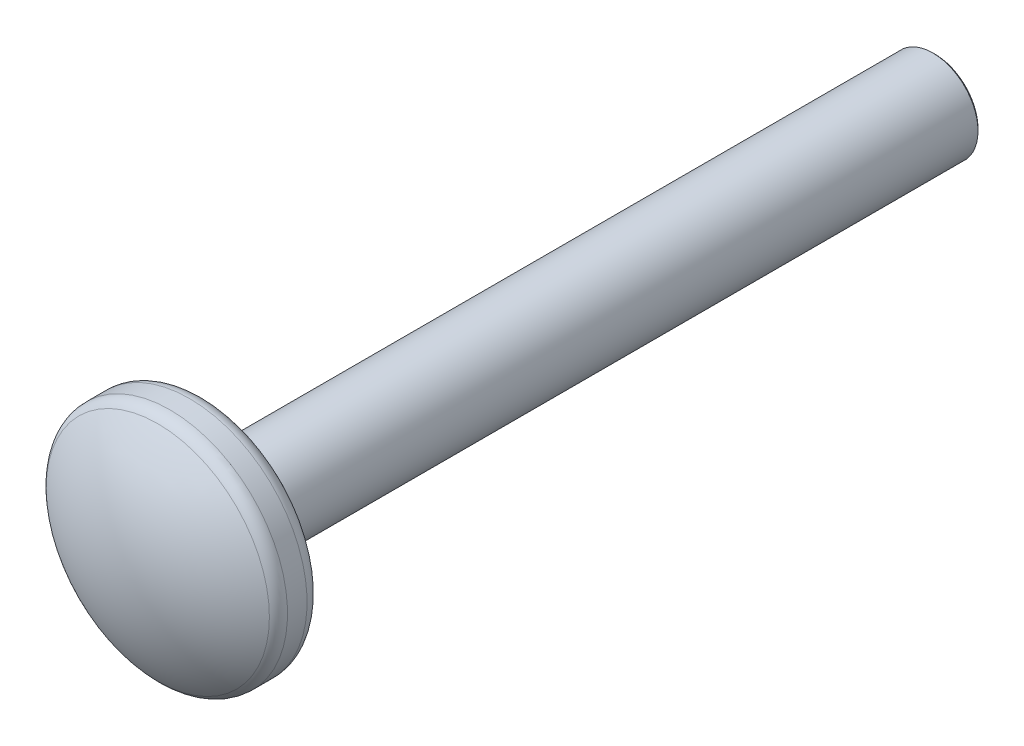
SolidWorks part; units mm, degrees
material "AISI 304"
ref_plane "Front Plane" through (0, 0, 0) normal (0, 0, 1) x (1, 0, 0)
ref_plane "Top Plane" through (0, 0, 0) normal (0, 1, 0) x (1, 0, 0)
ref_plane "Right Plane" through (0, 0, 0) normal (1, 0, 0) x (0, 0, -1)
sketch "Sketch1" plane through (0, 0, 0) normal (0, 0, 1) x (1, 0, 0)
  circle A0 centre (0, 0) radius 2.0828
  dimension "decimal equ" = 4.1656
curve "Helix/Spiral1" pitch 0.7937 height 26.1937 turns 33 parameters "helix length"=26.1937, "pitch"=0.7937
sketch "Sketch2" plane through (0, 0, 0) normal (1, 0, 0) x (0, 0, -1)
  line L0 (0.2977, 2.0828) -> (0.3969, 2.0828)
  line L1 (0.3969, 2.0828) -> (0.6945, 1.5672)
  line L2 (0.2977, 2.0828) -> (0, 1.5672)
  line L3 (0, 1.5672) -> (0.6945, 1.5672)
  line L4 (0.3473, 2.0828) -> (0.3473, 1.5672) construction
  line L6 (0.1488, 1.825) -> (0.5457, 1.825) construction
  line L7 (0, 1.5672) -> (0, 2.0828) construction
  line L8 (0, 2.0828) -> (0, -2.0828) construction
  line L9 (0, 2.0828) -> (0, -2.0828) construction
  point P8 (-3.2742, -2.0828)
  dimension "D1" = 60
  dimension "D3" = 0.0992
  dimension "D4" = 0.3969
  dimension "D2" = 3.2742
sketch "Sketch3" plane through (0, 0, 0) normal (1, 0, 0) x (0, 0, -1)
  line L0 (0, 0) -> (-25.4, 0) construction
  line L1 (0, 1.5672) -> (0.6945, 1.5672) construction
  line L2 (0, 0) -> (-25.4, 0)
  line L3 (0, 0) -> (0, 1.5672)
  line L4 (0, 1.5672) -> (-25.4, 1.5672)
  line L5 (-25.4, 0) -> (-25.4, 1.5672)
  dimension "length" = 25.4
revolve "Revolve1" add sketch "Sketch3" angle 360 about L0
sweep "Sweep1" [suppressed] add profiles "Sketch2" path "Helix/Spiral1"
sketch "Sketch39" plane through (0, 0, 0) normal (0, 0, -1) x (-1, 0, 0)
  circle A0 centre (0, 0) radius 2.0828 construction
  circle A1 centre (0, 0) radius 2.0828
extrude "Extrude5" [suppressed] cut sketch "Sketch39" along normal through all
sketch "Sketch38" plane through (0, 0, 0) normal (0, 0, -1) x (-1, 0, 0)
  circle A2 centre (0, 0) radius 1.4875
  circle A3 centre (0, 0) radius 1.4875
extrude "Extrude6" cut sketch "Sketch38" against normal through all draft 45 flip side to cut
sketch "Sketch10" plane through (0, 0, 0) normal (1, 0, 0) x (0, 0, -1)
  line L0 (0, 0) -> (23.0169, 0) construction
  line L1 (-279.4, 12.7) -> (-25.4, 12.7)
  line L2 (-279.4, 12.7) -> (-279.4, 0)
  line L3 (-279.4, 0) -> (-25.4, 0)
  line L4 (-25.4, 12.7) -> (-25.4, 0)
  line L5 (-25.4, 0) -> (-25.4, 1.5672) construction
  dimension "D1" = 254
  dimension "D2" = 12.7
revolve "Cut-Revolve2" [suppressed] cut sketch "Sketch10" angle 360 about L0
sketch "Sketch41" plane through (0, 0, 0) normal (1, 0, 0) x (0, 0, -1)
  line L0 (-25.4, 2.0828) -> (-25.4, 1.5672)
  line L1 (-25.4, 1.5672) -> (-24.5237, 1.5672)
  line L2 (-24.5237, 1.5672) -> (-24.0081, 2.0828)
  line L3 (-25.4, 2.0828) -> (-24.0081, 2.0828)
  line L4 (0, 1.5672) -> (0.6945, 1.5672) construction
  dimension "D1" = 0.8763
  dimension "D2" = 45
revolve "Cut-Revolve4" [suppressed] cut sketch "Sketch41" angle 360 about L2
sketch "Sketch8" plane through (0, 0, 0) normal (1, 0, 0) x (0, 0, -1)
  line L0 (0, 0) -> (-6.2449, 0) construction
  line L1 (-28.321, 0) -> (-25.4, 0)
  line L2 (-28.321, 0) -> (-28.321, 4.0894)
  line L3 (-28.321, 4.0894) -> (-25.4, 4.0894)
  line L4 (-25.4, 0) -> (-25.4, 4.0894)
  line L5 (-28.321, -4.0894) -> (-25.4, -4.0894) construction
  line L6 (-25.4, 0) -> (-25.4, 1.5672) construction
  dimension "head dia" = 8.1788
  dimension "head height" = 2.921
revolve "Revolve2" add sketch "Sketch8" angle 360 about L0
sketch "Sketch11" plane through (0, 0, 0) normal (1, 0, 0) x (0, 0, -1)
  line L0 (-26.8605, 4.0894) -> (-26.8605, -4.0894) construction
  line L1 (-28.321, 0) -> (-6.8951, 0) construction
  line L2 (-28.321, 4.0894) -> (-25.4, 4.0894) construction
  line L3 (-28.321, 0) -> (-28.321, 4.0894) construction
  line L4 (-26.6049, 4.0894) -> (-25.9258, 4.0894)
  line L6 (-25.4, 0) -> (-25.4, 4.0894) construction
  line L7 (-25.4, 3.5636) -> (-24.765, 3.5636)
  line L8 (-24.765, 3.5636) -> (-24.765, 4.7244)
  line L9 (-24.765, 4.7244) -> (-28.956, 4.7244)
  line L10 (-28.956, 4.7244) -> (-28.956, 0)
  line L11 (-28.956, 0) -> (-28.321, 0)
  arc A0 (-27.0251, 3.8796) -> (-28.321, 0) centre (-21.8656, 0) ccw
  arc A1 (-25.4, 3.5636) -> (-25.9258, 4.0894) centre (-25.9258, 3.5636) ccw
  arc A2 (-27.0251, 3.8796) -> (-26.6049, 4.0894) centre (-26.6049, 3.5636) cw
  dimension "D1" = 0.5258
  dimension "D2" = 0.635
  dimension "D3" = 0.635
  dimension "D4" = 0.635
revolve "Cut-Revolve3" cut sketch "Sketch11" angle 360 about L1
ref_plane "Plane1" through (0, 0, 28.321) normal (0, 0, 1) x (1, 0, 0)
sketch "Sketch12" plane through (0, 0, 28.321) normal (0, 0, 1) x (1, 0, 0)
  line L0 (0.508, 2.3264) -> (0.508, 1.1906)
  line L1 (0.508, 1.1906) -> (1.1906, 0.508) construction
  line L2 (1.1906, 0.508) -> (2.3264, 0.508)
  line L3 (0, 2.3813) -> (0, 0)
  line L4 (0, 0) -> (2.3813, 0)
  line L5 (0, 0) -> (0, 4.0894) construction
  line L6 (0, 0) -> (0.8493, 0.8493) construction
  line L7 (1.1906, 0) -> (1.1906, 1.5633) construction
  line L8 (0.508, 1.1906) -> (0.7079, 0.7079)
  line L9 (1.1906, 0.508) -> (0.7079, 0.7079)
  line L10 (0, 0) -> (0, -1.0114) construction
  line L11 (-0.508, 2.3264) -> (-0.508, 1.1906) construction
  arc A0 (2.3813, 0) -> (2.3264, 0.508) centre (0, 0) ccw
  arc A1 (0.508, 2.3264) -> (0, 2.3813) centre (0, 0) ccw
  arc A2 (-2.3813, 0) -> (-2.3264, 0.508) centre (0, 0) cw construction
  dimension "phillips dia" = 4.7625
  dimension "D2" = 45
  dimension "D4" = 22.5
  dimension "slot width" = 1.016
extrude "Cut-Extrude1" [suppressed] cut sketch "Sketch12" against normal blind 2.4829
draft "Draft3" [suppressed] type of draft neutral plane draft angle 15 neutral plane "Plane1" faces to draft 2 parameters "D1"=15
draft "Draft4" [suppressed] type of draft neutral plane draft angle 5 neutral plane "Plane1" faces to draft 4 parameters "D1"=5
pattern_circular "CirPattern1" [suppressed] count 4 over 360 about axis through (0, 0, 28.321) along (0, 0, -1) of bodies 110
ref_plane "Plane8" through (0, 0, 25.2439) normal (0, 0, -1) x (-1, 0, 0)
sketch "Sketch18" plane through (0, 0, 25.2439) normal (0, 0, 1) x (1, 0, 0)
  line L0 (0, 0) -> (0, 4.064) construction
  line L1 (1.5672, 0) -> (4.064, 0) construction
  circle A0 centre (0, 0) radius 4.064
  circle A1 centre (0, 0) radius 1.5672 construction
  circle A2 centre (0, 0) radius 1.5672 construction
  circle A3 centre (0, 0) radius 2.6908
  circle A4 centre (0, 0) radius 2.0828 construction
  point P8 (2.6908, 0)
  point P10 (0, 2.6908)
  dimension "washer dia." = 8.128
  dimension "D2" = 1.1235
sketch "Sketch21" plane through (0, 0, 25.2439) normal (0, 0, 1) x (1, 0, 0)
  circle A0 centre (0, 0) radius 2.6908
  circle A1 centre (0, 0) radius 1.5672
  circle A2 centre (0, 0) radius 2.0828 construction
extrude "Extrude2" add sketch "Sketch21" against normal blind 0.5842 separate body
ref_plane "Plane9" through (0, 2.6908, 0) normal (0, 1, 0) x (-1, 0, 0)
sketch "Sketch31" plane through (0, 2.6908, 0) normal (0, 1, 0) x (-1, 0, 0)
  line L1 (-0.508, 25.2439) -> (0.508, 25.2439)
  line L2 (-0.508, 25.2439) -> (-0.508, 24.6597)
  line L3 (-0.508, 24.6597) -> (0.508, 24.6597)
  line L4 (0.508, 25.2439) -> (0.508, 24.6597)
  line L5 (-2.6908, 24.6597) -> (2.6908, 24.6597) construction
  line L6 (0, 0) -> (0, 25.2439) construction
  line L7 (0.508, 24.9518) -> (-0.508, 24.9518) construction
  line L8 (0, 25.2439) -> (0, 24.6597) construction
  line L9 (2.6908, 25.2439) -> (-2.6908, 25.2439) construction
  dimension "D1" = 1.016
ref_plane "Plane10" through (0, 4.064, 0) normal (0, 1, 0) x (-1, 0, 0)
sketch "Sketch32" plane through (0, 4.064, 0) normal (0, 1, 0) x (-1, 0, 0)
  line L0 (-0.3775, 25.4) -> (-0.5773, 24.851)
  line L1 (-0.3775, 25.4) -> (0.5773, 25.0525)
  line L2 (-0.5773, 24.851) -> (0.3775, 24.5035)
  line L3 (0.5773, 25.0525) -> (0.3775, 24.5035)
  line L4 (-0.508, 25.2439) -> (-0.508, 24.6597) construction
  line L5 (-0.508, 24.6597) -> (0.508, 24.6597) construction
  line L6 (0.0999, 25.2263) -> (0, 24.9518) construction
  line L7 (0, 24.9518) -> (0.4774, 24.778) construction
  line L8 (0.508, 24.9518) -> (-0.508, 24.9518) construction
  line L9 (0, 0) -> (0, 6.2449) construction
  line L10 (-1.5672, 24.6597) -> (1.5672, 24.6597) construction
  dimension "D1" = 20
sketch "Sketch33" plane through (0, 2.6908, 0) normal (0, 1, 0) x (-1, 0, 0)
  line L1 (1.5672, 25.2439) -> (-1.5672, 25.2439) construction
  line L4 (0.508, 25.2439) -> (-0.508, 25.2439)
  line L5 (0.508, 24.6597) -> (0.508, 25.2439)
  line L6 (-0.508, 24.6597) -> (0.508, 24.6597)
  line L7 (-0.508, 25.2439) -> (-0.508, 24.6597)
  line L8 (0.508, 25.2439) -> (-0.508, 25.2439)
  line L9 (0.508, 24.6597) -> (0.508, 25.2439)
  line L10 (-0.508, 24.6597) -> (0.508, 24.6597)
  line L11 (-0.508, 25.2439) -> (-0.508, 24.6597)
  dimension "D1" = 0
extrude "Extrude3" [suppressed] add sketch "Sketch33" against normal up to next
loft "Loft2" [suppressed] add profiles "Sketch32", "Sketch31"
pattern_circular "CirPattern4" [suppressed] count 12 over 360 of bodies 185
sketch "Sketch40" plane through (0, 0, 0) normal (1, 0, 0) x (0, 0, -1)
  line L0 (-25.2439, 4.064) -> (-24.6597, 4.064) construction
  line L1 (-25.2439, -4.064) -> (-24.6597, -4.064) construction
  line L2 (-24.9518, 4.064) -> (-24.9518, -4.064) construction
  line L3 (-24.9518, 0) -> (0, 0) construction
  line L4 (0, -1.4875) -> (0, 1.4875) construction
  line L6 (-25.2439, -5.9931) -> (-25.2439, 5.9931) construction
  dimension "D1" = 0.5842
  dimension "D2" = 8.128
equation "\"D3@Sketch2\" = \"pitch@Helix/Spiral1\"*.125"
equation "\"D4@Sketch2\" = \"pitch@Helix/Spiral1\"*.5"
equation "\"D1@Sketch11\" = \"head height@Sketch8\"*.18"
equation "\"D1@Cut-Extrude1\" = \"head height@Sketch8\"*.85"
equation "\"D1@Sketch31\" = \"washer dia.@Sketch18\"*.125"
equation "\"helix length@Helix/Spiral1\" = \"length@Sketch3\" + \"pitch@Helix/Spiral1\""
equation "\"D1@Sketch38\" = \"pitch@Helix/Spiral1\"*.750"
equation "\"D1@Plane8\" = \"D2@Sketch32\""
equation "\"D2@Sketch18\" = \"D1@Sketch18\"*.45"
equation "\"D2@Sketch2\" = \"pitch@Helix/Spiral1\"*4.125"
equation "\"D1@Sketch40\" = \"washer width@Extrude2\""
equation "\"D2@Sketch40\" = \"washer dia.@Sketch18\""
equation "\"D1@Sketch41\" = \"washer width@Extrude2\"*1.50"
